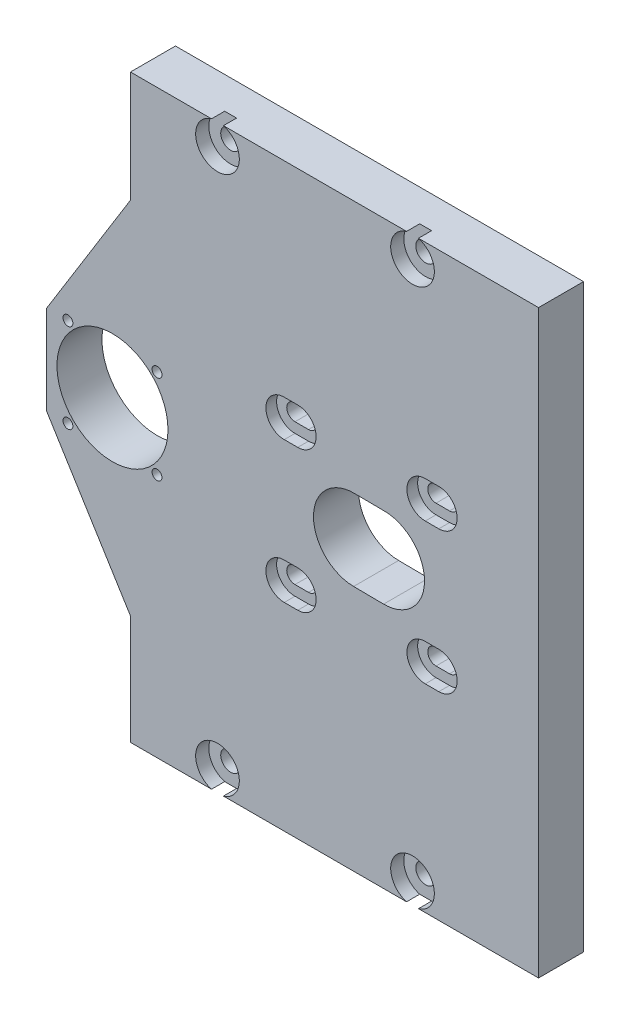
SolidWorks part; units mm, degrees
ref_plane "Front Plane" through (0, 0, 0) normal (0, 0, 1) x (1, 0, 0)
ref_plane "Top Plane" through (0, 0, 0) normal (0, 1, 0) x (1, 0, 0)
ref_plane "Right Plane" through (0, 0, 0) normal (1, 0, 0) x (0, 0, -1)
sketch "Sketch1" plane through (0, 0, 0) normal (0, 0, 1) x (1, 0, 0)
  line L24 (-148, 255) -> (-148, 190) construction
  line L31 (-148, 70) -> (-148, 10) construction
  line L32 (-148, 33.5) -> (-12, 33.5) construction
  line L36 (-12, 227) -> (-148, 227) construction
  line L37 (-148, 227) -> (-148, 190)
  line L38 (-148, 70) -> (-148, 33.5)
  line L39 (-148, 33.5) -> (-12, 33.5)
  line L43 (-12, 227) -> (-148, 227)
  line L44 (-176, 115.2267) -> (-176, 144.7733) construction
  line L45 (-176, 115.2267) -> (-176, 144.7733)
  line L46 (-176, 144.7733) -> (-148, 190)
  line L47 (-176, 115.2267) -> (-148, 70)
  line L51 (-12, 33.5) -> (-12, 227)
  circle A8 centre (-154, 130) radius 18.5
  circle A9 centre (-154, 130) radius 18.5
  dimension "D1" = 0.5
extrude "Boss-Extrude1" add sketch "Sketch1" along normal blind 15
sketch "Sketch2" plane through (0, 0, 15) normal (0, 0, 1) x (1, 0, 0)
  circle A1 centre (-139.1508, 115.1508) radius 2.25
  circle A3 centre (-168.8492, 115.1508) radius 2.25
  circle A5 centre (-168.8492, 144.8492) radius 2.25
  circle A7 centre (-139.1508, 144.8492) radius 2.25
hole_wizard "M4x0.7 Tapped Hole1" positions "Sketch3" profile "Sketch4" tap size "M4x0.7" standard "ANSI Metric"
sketch "Sketch3" plane through (0, 0, 15) normal (0, 0, 1) x (1, 0, 0)
  point P0 (-168.8492, 144.8492)
  point P3 (-139.1508, 144.8492)
  point P6 (-139.1508, 115.1508)
  point P9 (-168.8492, 115.1508)
sketch "Sketch4" plane through (-168.8492, 144.8492, 15) normal (1, 0, 0) x (0, -1, 0)
  line L0 (0, 0) -> (0, 14.1)
  line L1 (0, 14.1) -> (1.65, 13.1086)
  line L2 (1.65, 13.1086) -> (1.65, 0)
  line L5 (1.65, 0) -> (0, 0)
  line L10 (0, 14.1) -> (-1.65, 13.1086) construction
  line L11 (0, -6.35) -> (0, 107.95) construction
  dimension "Tap Drill Dia." = 3.3
  dimension "Tap Drill Depth" = 14.1
  dimension "Drill Angle" = 118
cosmetic thread "Hole Thread1" parameters "D1"=12, "D2"=4
cosmetic thread "Hole Thread2" parameters "D1"=12, "D2"=4
cosmetic thread "Hole Thread3" parameters "D1"=12, "D2"=4
cosmetic thread "Hole Thread4" parameters "D1"=12, "D2"=4
hole_wizard "CBORE for M6 Hex Head Bolt1" positions "Sketch5" profile "Sketch6" counterbore size "M6" standard "ANSI Metric"
sketch "Sketch5" plane through (0, 0, 15) normal (0, 0, 1) x (1, 0, 0)
  point P0 (-54, 220)
  point P3 (-119, 220)
  point P6 (-54, 40.5)
  point P9 (-119, 40.5)
sketch "Sketch6" plane through (-54, 220, 15) normal (1, 0, 0) x (0, -1, 0)
  line L0 (0, 0) -> (0, 29.9828)
  line L1 (0, 29.9828) -> (3.3, 28)
  line L2 (3.3, 28) -> (3.3, 4.38)
  line L3 (3.3, 4.38) -> (7.275, 4.38)
  line L4 (7.275, 4.38) -> (7.275, 0)
  line L5 (7.275, 0) -> (0, 0)
  line L10 (0, 29.9828) -> (-3.3, 28) construction
  line L11 (0, -6.35) -> (0, 107.95) construction
  dimension "Hole Dia." = 6.6
  dimension "Hole Depth" = 28
  dimension "C'Bore Dia." = 14.55
  dimension "C'Bore Depth" = 4.38
  dimension "Drill Angle" = 118
sketch "Sketch7" plane through (0, 0, 15) normal (0, 0, 1) x (1, 0, 0)
  line L0 (-73.5, 129.1439) -> (-88.5, 129.1439)
  line L1 (-89.5, 152.6439) -> (-94.5, 152.6439)
  line L2 (-42.5, 152.6439) -> (-47.5, 152.6439)
  line L3 (-42.5, 105.6439) -> (-47.5, 105.6439)
  line L4 (-89.5, 105.6439) -> (-94.5, 105.6439)
  circle A1 centre (-50, 105.6439) radius 2.85 construction
  circle A2 centre (-73.5, 129.1439) radius 13.5
  circle A3 centre (-73.5, 129.1439) radius 13.5
  circle A4 centre (-97, 105.6439) radius 2.85 construction
  circle A5 centre (-97, 152.6439) radius 2.85 construction
  circle A6 centre (-50, 152.6439) radius 2.85 construction
  circle A7 centre (-50, 105.6439) radius 2.85
  circle A8 centre (-97, 105.6439) radius 2.85
  circle A9 centre (-97, 152.6439) radius 2.85
  circle A10 centre (-50, 152.6439) radius 2.85
  dimension "D1" = 1
hole_wizard "Ø1.0mm Dowel Slot1" positions "Sketch8" profile "Sketch9" size "Ø1.0" standard "ANSI Metric" slot yes
sketch "Sketch8" plane through (0, 0, 15) normal (0, 0, 1) x (1, 0, 0)
  line L0 (-86.9991, 129.3233) -> (-50.0009, 128.9645) construction
  point P0 (-68.5, 129.1439)
  dimension "D1" = 37
sketch "Sketch9" plane through (-68.5, 129.1439, 15) normal (1, 0, 0) x (0, -1, 0)
  line L0 (0, 0) -> (0, 36.1116)
  line L1 (0, 36.1116) -> (13.5, 28)
  line L2 (13.5, 28) -> (13.5, 0)
  line L5 (13.5, 0) -> (0, 0)
  line L10 (0, 36.1116) -> (-13.5, 28) construction
  line L11 (0, -6.35) -> (0, 107.95) construction
  dimension "Hole Dia." = 27
  dimension "Hole Depth" = 28
  dimension "Drill Angle" = 118
hole_wizard "CBORE SLOT for M5 Hex Head Bolt1" positions "Sketch10" profile "Sketch11" size "M5" standard "ANSI Metric" slot yes
sketch "Sketch10" plane through (0, 0, 15) normal (0, 0, 1) x (1, 0, 0)
  line L0 (-99.5, 152.6439) -> (-89.5, 152.6439) construction
  point P0 (-94.5, 152.6439)
  point P5 (-94.5, 105.6439)
  point P8 (-47.5, 152.6439)
  point P11 (-47.5, 105.6439)
  dimension "D1" = 10
sketch "Sketch11" plane through (-94.5, 152.6439, 15) normal (1, 0, 0) x (0, -1, 0)
  line L0 (0, 0) -> (0, 29.6524)
  line L1 (0, 29.6524) -> (2.75, 28)
  line L2 (2.75, 28) -> (2.75, 3.58)
  line L3 (2.75, 3.58) -> (6.12, 3.58)
  line L4 (6.12, 3.58) -> (6.12, 0)
  line L5 (6.12, 0) -> (0, 0)
  line L10 (0, 29.6524) -> (-2.75, 28) construction
  line L11 (0, -6.35) -> (0, 107.95) construction
  dimension "Hole Dia." = 5.5
  dimension "Hole Depth" = 28
  dimension "C'Bore Dia." = 12.24
  dimension "C'Bore Depth" = 3.58
  dimension "Drill Angle" = 118
